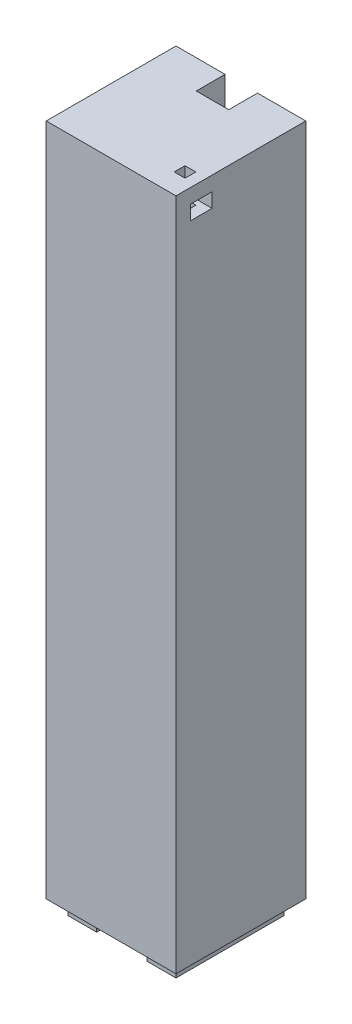
SolidWorks part; units mm, degrees
ref_plane "Front Plane" through (0, 0, 0) normal (0, 0, 1) x (1, 0, 0)
ref_plane "Top Plane" through (0, 0, 0) normal (0, 1, 0) x (1, 0, 0)
ref_plane "Right Plane" through (0, 0, 0) normal (1, 0, 0) x (0, 0, -1)
sketch "Sketch1" plane through (0, 0, 0) normal (0, 1, 0) x (1, 0, 0)
  line L1 (0, 0) -> (36, 0)
  line L2 (0, 0) -> (0, 36)
  line L3 (0, 36) -> (36, 36)
  line L4 (36, 0) -> (36, 36)
  dimension "D1" = 36
  dimension "D2" = 36
extrude "Boss-Extrude1" add sketch "Sketch1" along normal blind 186.9
sketch "Sketch2" plane through (0, 0, 0) normal (0, -1, 0) x (1, 0, 0)
  line L0 (0, 0) -> (36, 0) construction
  line L1 (3, -3) -> (7, -3)
  line L2 (3, -3) -> (3, -33)
  line L3 (3, -33) -> (7, -33)
  line L4 (7, -11) -> (7, -25)
  line L5 (36, -36) -> (0, -36) construction
  line L6 (0, -36) -> (0, 0) construction
  line L20 (36, 0) -> (36, -36) construction
  line L29 (7, -3) -> (11, -3)
  line L31 (7, -11) -> (11, -11)
  line L32 (11, -3) -> (11, -11)
  line L33 (7, -25) -> (11, -25)
  line L35 (7, -33) -> (11, -33)
  line L36 (11, -25) -> (11, -33)
  line L45 (29, -3) -> (33, -3)
  line L46 (29, -11) -> (29, -25)
  line L47 (29, -33) -> (33, -33)
  line L48 (33, -3) -> (33, -33)
  line L50 (29, -3) -> (25, -3)
  line L52 (29, -11) -> (25, -11)
  line L53 (25, -3) -> (25, -11)
  line L54 (29, -33) -> (25, -33)
  line L56 (29, -25) -> (25, -25)
  line L57 (25, -33) -> (25, -25)
  dimension "D1" = 3
  dimension "D2" = 3
  dimension "D3" = 3
  dimension "D4" = 4
  dimension "D5" = 4
  dimension "D6" = 8
  dimension "D7" = 8
  dimension "D8" = 4
  dimension "D9" = 3
  dimension "D10" = 3
  dimension "D11" = 3
  dimension "D12" = 4
  dimension "D13" = 4
  dimension "D14" = 4
extrude "Boss-Extrude2" add sketch "Sketch2" along normal blind 4
sketch "Sketch3" plane through (0, 0, 0) normal (0, -1, 0) x (1, 0, 0)
  line L0 (36, -36) -> (0, -36) construction
  line L2 (0, -36) -> (0, 0) construction
  circle A0 centre (18, -18) radius 2
  dimension "D1" = 4
  dimension "D2" = 18
  dimension "D3" = 18
extrude "Cut-Extrude1" cut sketch "Sketch3" against normal blind 5
sketch "Sketch4" plane through (0, 0, -36) normal (0, 0, 1) x (1, 0, 0)
  line L0 (0, 186.9) -> (36, 186.9) construction
  line L1 (13.62, 186.9) -> (22.62, 186.9)
  line L2 (13.62, 186.9) -> (13.62, 0)
  line L3 (13.62, 0) -> (22.62, 0)
  line L4 (22.62, 186.9) -> (22.62, 0)
  line L5 (0, 0) -> (36, 0) construction
  line L7 (36, 186.9) -> (36, 0) construction
  dimension "D1" = 13.38
  dimension "D2" = 9
extrude "Cut-Extrude2" cut sketch "Sketch4" along normal blind 8
sketch "Sketch5" plane through (36, 0, 0) normal (1, 0, 0) x (0, 0, -1)
  line L0 (0, 186.9) -> (36, 186.9) construction
  line L1 (4, 182.9) -> (10, 182.9)
  line L2 (4, 182.9) -> (4, 178.9)
  line L3 (4, 178.9) -> (10, 178.9)
  line L4 (10, 182.9) -> (10, 178.9)
  line L5 (0, 186.9) -> (0, 0) construction
  dimension "D1" = 6
  dimension "D2" = 4
  dimension "D3" = 4
  dimension "D4" = 4
extrude "Cut-Extrude3" cut sketch "Sketch5" against normal blind 9
sketch "Sketch6" plane through (0, 186.9, 0) normal (0, 1, 0) x (1, 0, 0)
  line L0 (36, 0) -> (36, 36) construction
  line L1 (30, 8.5) -> (33, 8.5)
  line L2 (30, 8.5) -> (30, 5.5)
  line L3 (30, 5.5) -> (33, 5.5)
  line L4 (33, 8.5) -> (33, 5.5)
  line L5 (0, 0) -> (36, 0) construction
  dimension "D1" = 3
  dimension "D2" = 3
  dimension "D3" = 3
  dimension "D4" = 5.5
extrude "Cut-Extrude4" cut sketch "Sketch6" against normal blind 10
